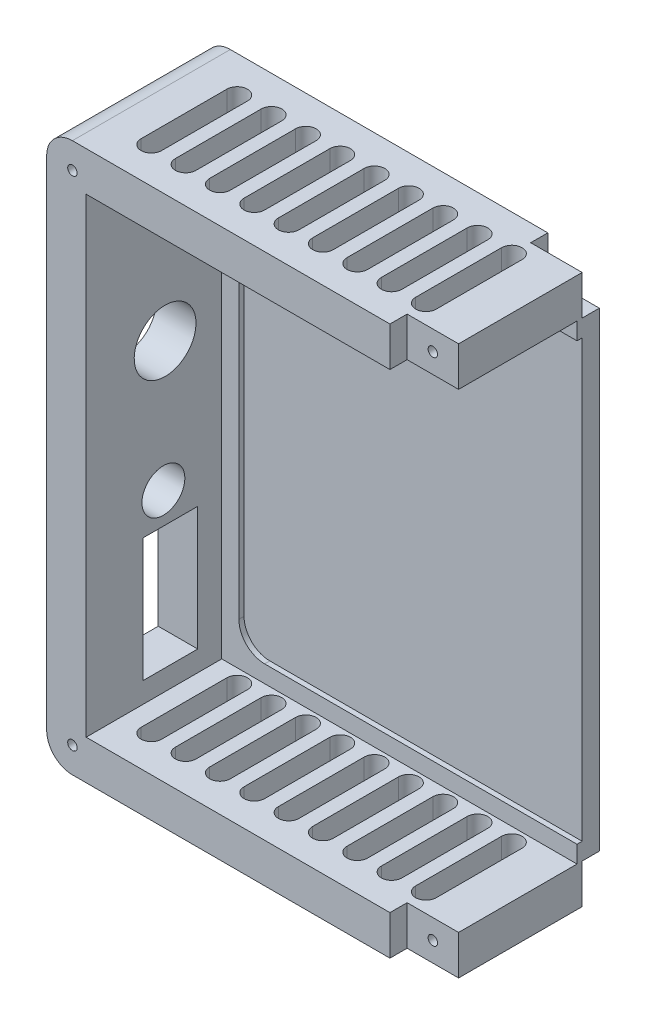
SolidWorks part; units mm, degrees
ref_plane "Front Plane" through (0, 0, 0) normal (0, 0, 1) x (1, 0, 0)
ref_plane "Top Plane" through (0, 0, 0) normal (0, 1, 0) x (1, 0, 0)
ref_plane "Right Plane" through (0, 0, 0) normal (1, 0, 0) x (0, 0, -1)
sketch "Sketch1" plane through (0, 0, 0) normal (0, 0, 1) x (1, 0, 0)
  line L1 (-115, 80) -> (115, 80)
  line L2 (-115, 80) -> (-115, -80)
  line L3 (-115, -80) -> (115, -80)
  line L4 (115, 80) -> (115, -80)
  line L5 (-115, 80) -> (115, -80) construction
  line L6 (-115, -80) -> (115, 80) construction
  point P0 (0, 0)
  dimension "D1" = 230
  dimension "D2" = 160
extrude "Boss-Extrude1" add sketch "Sketch1" along normal blind 46
shell "Shell1" thickness 11.5 removed face at (0, 0, 46)
sketch "Sketch2" plane through (-115, 0, 0) normal (-1, 0, 0) x (0, 0, 1)
  line L1 (29.5, -26.5) -> (13.5, -26.5)
  line L2 (29.5, -26.5) -> (29.5, -62.5)
  line L3 (29.5, -62.5) -> (13.5, -62.5)
  line L4 (13.5, -26.5) -> (13.5, -62.5)
  line L5 (29.5, -26.5) -> (13.5, -62.5) construction
  line L6 (29.5, -62.5) -> (13.5, -26.5) construction
  line L7 (46, -80) -> (0, -80) construction
  line L9 (46, 80) -> (0, 80) construction
  line L10 (46, 80) -> (46, -80) construction
  circle A0 centre (23.5, -17.5) radius 6.25
  circle A1 centre (23, 20) radius 9
  point P0 (21.5, -44.5)
  dimension "D4" = 9
  dimension "D6" = 12.5
  dimension "D7" = 18
  dimension "D1" = 53.5
  dimension "D2" = 36
  dimension "D3" = 22.5
  dimension "D5" = 16
  dimension "D8" = 60
  dimension "D9" = 23
  dimension "D10" = 16.5
extrude "Cut-Extrude1" cut sketch "Sketch2" against normal up to surface (11.5 mm away) up to face at (-103.5, 0, 28.75)
sketch "Sketch3" plane through (0, 0, 46) normal (0, 0, 1) x (1, 0, 0)
  line L0 (115, 80) -> (-115, 80) construction
  line L1 (-115, -80) -> (115, -80) construction
  line L2 (0, 80) -> (115, 80)
  line L3 (0, 80) -> (0, -80)
  line L4 (0, -80) -> (115, -80)
  line L5 (115, 80) -> (115, -80)
  dimension "D1" = 115
extrude "Cut-Extrude2" cut sketch "Sketch3" against normal up to surface (46 mm away) up to face at (0, 0, 0)
ref_plane "Plane1" through (0, 0, 23) normal (0, 0, 1) x (1, 0, 0)
sketch "Sketch13" plane through (0, -80, 0) normal (0, -1, 0) x (1, 0, 0)
  line L0 (-98, 35.5) -> (-98, 10.5)
  line L1 (-92, 10.5) -> (-92, 35.5)
  line L2 (-88, 35.5) -> (-88, 10.5)
  line L3 (-115, 46) -> (0, 46) construction
  line L4 (-115, 46) -> (-115, 0) construction
  line L5 (-82, 10.5) -> (-82, 35.5)
  line L6 (-78, 35.5) -> (-78, 10.5)
  line L7 (-72, 10.5) -> (-72, 35.5)
  line L8 (-68, 35.5) -> (-68, 10.5)
  line L9 (-62, 10.5) -> (-62, 35.5)
  line L10 (-58, 35.5) -> (-58, 10.5)
  line L11 (-52, 10.5) -> (-52, 35.5)
  line L12 (-48, 35.5) -> (-48, 10.5)
  line L13 (-42, 10.5) -> (-42, 35.5)
  line L14 (-38, 35.5) -> (-38, 10.5)
  line L15 (-32, 10.5) -> (-32, 35.5)
  line L16 (-28, 35.5) -> (-28, 10.5)
  line L17 (-22, 10.5) -> (-22, 35.5)
  line L18 (-18, 35.5) -> (-18, 10.5)
  line L19 (-12, 10.5) -> (-12, 35.5)
  line L22 (-8, 35.5) -> (-8, 10.5) [skipped]
  line L23 (-2, 10.5) -> (-2, 35.5) [skipped]
  arc A0 (-98, 10.5) -> (-92, 10.5) centre (-95, 10.5) ccw
  arc A1 (-92, 35.5) -> (-98, 35.5) centre (-95, 35.5) ccw
  arc A2 (-82, 35.5) -> (-88, 35.5) centre (-85, 35.5) ccw
  arc A3 (-88, 10.5) -> (-82, 10.5) centre (-85, 10.5) ccw
  arc A4 (-72, 35.5) -> (-78, 35.5) centre (-75, 35.5) ccw
  arc A5 (-78, 10.5) -> (-72, 10.5) centre (-75, 10.5) ccw
  arc A6 (-62, 35.5) -> (-68, 35.5) centre (-65, 35.5) ccw
  arc A7 (-68, 10.5) -> (-62, 10.5) centre (-65, 10.5) ccw
  arc A8 (-52, 35.5) -> (-58, 35.5) centre (-55, 35.5) ccw
  arc A9 (-58, 10.5) -> (-52, 10.5) centre (-55, 10.5) ccw
  arc A10 (-42, 35.5) -> (-48, 35.5) centre (-45, 35.5) ccw
  arc A11 (-48, 10.5) -> (-42, 10.5) centre (-45, 10.5) ccw
  arc A12 (-32, 35.5) -> (-38, 35.5) centre (-35, 35.5) ccw
  arc A13 (-38, 10.5) -> (-32, 10.5) centre (-35, 10.5) ccw
  arc A14 (-22, 35.5) -> (-28, 35.5) centre (-25, 35.5) ccw
  arc A15 (-28, 10.5) -> (-22, 10.5) centre (-25, 10.5) ccw
  arc A16 (-12, 35.5) -> (-18, 35.5) centre (-15, 35.5) ccw
  arc A17 (-18, 10.5) -> (-12, 10.5) centre (-15, 10.5) ccw
  arc A20 (-2, 35.5) -> (-8, 35.5) centre (-5, 35.5) ccw [skipped]
  arc A21 (-8, 10.5) -> (-2, 10.5) centre (-5, 10.5) ccw [skipped]
  point P6 (-95, 38.5)
  dimension "D1" = 3
  dimension "D4" = 17
  dimension "D2" = 25
  dimension "D3" = 7.5
  dimension "D5" = 10
extrude "Cut-Extrude12" cut sketch "Sketch13" against normal blind 12
mirror "Mirror13" about plane through (0, 0, 0) normal (0, 1, 0) of "Cut-Extrude12"
sketch "Sketch15" plane through (0, 0, 11.5) normal (0, 0, 1) x (1, 0, 0)
  line L0 (-103.5, 68.5) -> (-103.5, -68.5) construction
  line L1 (-103.5, -68.5) -> (0, -68.5)
  line L2 (-103.5, -68.5) -> (-103.5, 68.5)
  line L3 (-103.5, 68.5) -> (0, 68.5)
  line L4 (0, -68.5) -> (0, 68.5)
  line L5 (-103.5, -68.5) -> (0, 68.5) construction
  line L6 (-103.5, 68.5) -> (0, -68.5) construction
  line L7 (-103.5, -68.5) -> (-98, -68.5) construction
  line L8 (0, 68.5) -> (0, -68.5) construction
  line L9 (-98, 68.5) -> (-103.5, 68.5) construction
  point P0 (-51.75, 0)
extrude "Cut-Extrude14" cut sketch "Sketch15" against normal blind 5
fillet "Fillet1" radius 7.5 2 edges at (-115, 80, 23) (-115, -80, 23)
sketch "Sketch17" plane through (0, 0, 6.5) normal (0, 0, 1) x (1, 0, 0)
  line L0 (-103.5, 68.5) -> (-103.5, -68.5) construction
  line L1 (-91, -63.5) -> (-12.5, -63.5)
  line L2 (-98.5, -56) -> (-98.5, 56)
  line L3 (-91, 63.5) -> (-12.5, 63.5)
  line L4 (-12.5, -63.5) -> (0, -63.5)
  line L7 (-103.5, -68.5) -> (0, -68.5) construction
  line L8 (0, 68.5) -> (-103.5, 68.5) construction
  line L10 (0, -68.5) -> (0, 68.5) construction
  line L11 (-12.5, 63.5) -> (0, 63.5)
  line L12 (0, -63.5) -> (0, 63.5)
  arc A2 (-98.5, 56) -> (-91, 63.5) centre (-91, 56) cw
  arc A3 (-91, -63.5) -> (-98.5, -56) centre (-91, -56) cw
  point P0 (-51.75, 0)
  dimension "D1" = 5
  dimension "D2" = 5
  dimension "D3" = 5
extrude "Cut-Extrude15" cut sketch "Sketch17" against normal blind 1.5
sketch "Sketch18" plane through (0, 0, 46) normal (0, 0, 1) x (1, 0, 0)
  line L0 (-107.5, -80) -> (0, -80) construction
  line L1 (-115, 72.5) -> (-115, -72.5) construction
  line L2 (0, 80) -> (-107.5, 80) construction
  circle A0 centre (-107.5, -72.5) radius 1.375
  circle A1 centre (-107.5, 72.5) radius 1.375
  dimension "D1" = 2.75
  dimension "D2" = 2.75
  dimension "D3" = 7.5
  dimension "D4" = 7.5
  dimension "D5" = 7.5
  dimension "D6" = 7.5
extrude "Cut-Extrude16" cut sketch "Sketch18" against normal blind 10
sketch "Sketch19" plane through (0, 0, 46) normal (0, 0, 1) x (1, 0, 0)
  line L0 (0, -68.5) -> (0, -80) construction
  line L1 (-15, -68.5) -> (15, -68.5)
  line L2 (-15, -68.5) -> (-15, -80)
  line L3 (-15, -80) -> (15, -80)
  line L4 (15, -68.5) -> (15, -80)
  line L5 (-15, -68.5) -> (15, -80) construction
  line L6 (-15, -80) -> (15, -68.5) construction
  line L7 (-107.5, -80) -> (0, -80) construction
  line L8 (-103.5, -68.5) -> (0, -68.5) construction
  point P0 (0, -74.25)
  dimension "D1" = 30
extrude "Cut-Extrude17" cut sketch "Sketch19" against normal blind 5
sketch "Sketch20" plane through (0, 0, 41) normal (0, 0, 1) x (1, 0, 0)
  line L0 (0, -80) -> (0, -68.5) construction
  line L2 (-15, -80) -> (0, -80) construction
  circle A0 centre (-7.5, -74.25) radius 1.375
  point P4 (0, -74.25)
  dimension "D1" = 2.75
  dimension "D2" = 7.5
  dimension "D3" = 5.75
extrude "Cut-Extrude18" cut sketch "Sketch20" against normal blind 8
mirror "Mirror14" about plane through (0, 0, 0) normal (0, 1, 0) of "Cut-Extrude17", "Cut-Extrude18"
sketch "Sketch21" plane through (0, 0, 0) normal (0, 0, -1) x (-1, 0, 0)
  line L0 (0, -80) -> (0, 80) construction
  line L1 (15, 68.5) -> (-15, 68.5)
  line L2 (15, 68.5) -> (15, 80)
  line L3 (15, 80) -> (-15, 80)
  line L4 (-15, 68.5) -> (-15, 80)
  line L5 (15, 68.5) -> (-15, 80) construction
  line L6 (15, 80) -> (-15, 68.5) construction
  line L7 (0, 80) -> (107.5, 80) construction
  point P0 (0, 74.25)
  dimension "D1" = 11.5
  dimension "D2" = 30
extrude "Cut-Extrude19" cut sketch "Sketch21" against normal blind 5
sketch "Sketch22" plane through (0, 0, 5) normal (0, 0, -1) x (-1, 0, 0)
  line L0 (15, 80) -> (0, 80) construction
  line L1 (0, 80) -> (0, 68.5) construction
  circle A0 centre (7.5, 74.25) radius 1.375
  dimension "D1" = 2.75
  dimension "D2" = 5.75
  dimension "D3" = 7.5
extrude "Cut-Extrude20" cut sketch "Sketch22" against normal blind 8
mirror "Mirror15" about plane through (0, 0, 0) normal (0, 1, 0) of "Cut-Extrude19", "Cut-Extrude20"
